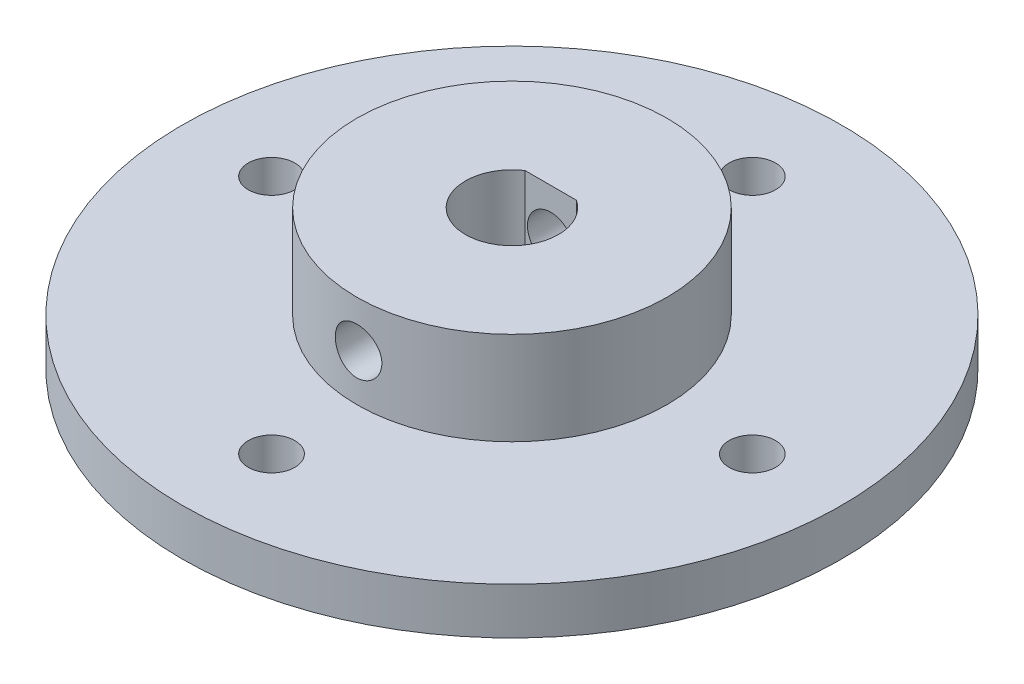
SolidWorks part; units mm, degrees
ref_plane "Front Plane" through (0, 0, 0) normal (0, 0, 1) x (1, 0, 0)
ref_plane "Top Plane" through (0, 0, 0) normal (0, 1, 0) x (1, 0, 0)
ref_plane "Right Plane" through (0, 0, 0) normal (1, 0, 0) x (0, 0, -1)
sketch "Sketch1" plane through (0, 0, 0) normal (0, 1, 0) x (1, 0, 0)
  line L0 (-1.6583, 2.5) -> (1.6583, 2.5)
  circle A0 centre (0, 0) radius 21.25
  circle A1 centre (0, 0) radius 15.5 construction
  circle A2 centre (0, 0) radius 3 construction
  circle A3 centre (0, 15.5) radius 1.5
  circle A4 centre (15.5, 0) radius 1.5
  circle A5 centre (0, -15.5) radius 1.5
  circle A6 centre (-15.5, 0) radius 1.5
  arc A7 (-1.6583, 2.5) -> (1.6583, 2.5) centre (0, 0) ccw
  circle A8 centre (0, 0) radius 10
  dimension "D1" = 6
  dimension "D2" = 31
  dimension "D3" = 42.5
  dimension "D4" = 3
  dimension "D5" = 2.5
  dimension "D6" = 20
extrude "Boss-Extrude1" add sketch "Sketch1" against normal blind 3 contours A0 A8 A6 A5 A4 A3 | A8 A7 L0 region at (-20.649, 0, 0) region at (-9.7172, 0, 0)
extrude "Boss-Extrude2" add sketch "Sketch1<4>" along normal blind 6 contours A8 A7 L0 region at (-9.7172, 0, 0)
sketch "Sketch1<4>" plane through (0, 0, 0) normal (0, 1, 0) x (1, 0, 0) same geometry as "Sketch1"
sketch "Sketch2" plane through (0, 0, -2.5) normal (0, 0, 1) x (1, 0, 0)
  line L0 (-1.6583, 6) -> (1.6583, 6) construction
  circle A0 centre (0, 3) radius 1.5
  point P4 (0, 0)
  point P5 (0, 0)
  point P6 (0, 6)
  dimension "D2" = 3
  dimension "D1" = 3
extrude "Cut-Extrude1" cut sketch "Sketch2" against normal through all both and the other way through all
